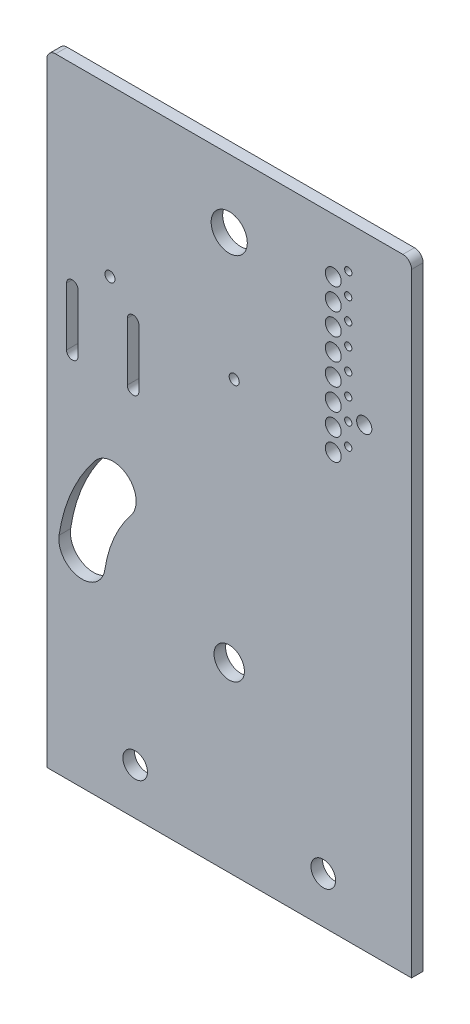
SolidWorks part; units mm, degrees
ref_plane "Ön Düzlem" through (0, 0, 0) normal (0, 0, 1) x (1, 0, 0)
ref_plane "Üst Düzlem" through (0, 0, 0) normal (0, 1, 0) x (1, 0, 0)
ref_plane "Sağ Düzlem" through (0, 0, 0) normal (1, 0, 0) x (0, 0, -1)
sketch "Model" plane through (0, 0, 0) normal (0, 0, 1) x (1, 0, 0)
  line L0 (2205.6968, 1653.3829) -> (2213.2595, 1658.0286) construction
  line L1 (2211.0042, 1661.2461) -> (2203.4116, 1656.7808) construction
  line L4 (2215.7762, 1634.375) -> (2223.3388, 1639.0206) construction
  line L5 (2221.0836, 1642.2381) -> (2213.4909, 1637.7728) construction
  line L8 (2098.8929, 1585.6212) -> (2224.8929, 1585.6212)
  line L9 (2224.8929, 1585.6212) -> (2224.8929, 1800.6212)
  line L10 (2224.8929, 1800.6212) -> (2098.8929, 1800.6212)
  line L11 (2098.8929, 1800.6212) -> (2098.8929, 1585.6212)
  circle A0 centre (2129.4379, 1602.5117) radius 4.5
  circle A1 centre (2194.4379, 1602.5117) radius 4.5
  circle A2 centre (2161.8929, 1777.1976) radius 6.25
  circle A3 centre (2161.8929, 1648.5151) radius 5.25
  circle A4 centre (2197.8384, 1781.8976) radius 2.75
  circle A5 centre (2203.0172, 1786.1566) radius 1.25
  circle A6 centre (2197.8336, 1774.3976) radius 2.75
  circle A7 centre (2203.0124, 1778.6566) radius 1.25
  circle A8 centre (2197.8347, 1766.8976) radius 2.75
  circle A9 centre (2203.0135, 1771.1566) radius 1.25
  circle A10 centre (2197.8341, 1759.3976) radius 2.75
  circle A11 centre (2203.0129, 1763.6566) radius 1.25
  circle A12 centre (2197.8353, 1751.8976) radius 2.75
  circle A13 centre (2203.0141, 1756.1566) radius 1.25
  circle A14 centre (2197.836, 1744.3976) radius 2.75
  circle A15 centre (2203.0148, 1748.6566) radius 1.25
  circle A16 centre (2197.8336, 1736.8976) radius 2.75
  circle A17 centre (2203.0124, 1741.1566) radius 1.25
  circle A18 centre (2197.8336, 1729.3976) radius 2.75
  circle A19 centre (2203.0124, 1733.6566) radius 1.25
  circle A20 centre (2208.5322, 1742.9332) radius 2.625
  circle A21 centre (2163.6193, 1734.1117) radius 1.75
  circle A22 centre (2120.6953, 1743.3824) radius 1.75
  spline S1 degree 3 poles (2213.2595, 1658.0286) (2213.935, 1660.1178) (2213.1833, 1661.1903) (2211.0042, 1661.2461) knots 0.25 0.25 0.25 0.25 0.375 0.375 0.375 0.375 construction
  spline S2 degree 2 poles (2203.4116, 1656.7808) (2202.3354, 1653.552) (2205.6968, 1653.3829) knots 0.75 0.75 0.75 1 1 1 construction
  spline S3 degree 3 poles (2223.3388, 1639.0206) (2224.0144, 1641.1098) (2223.2626, 1642.1823) (2221.0836, 1642.2381) knots 0.25 0.25 0.25 0.25 0.375 0.375 0.375 0.375 construction
  spline S4 degree 2 poles (2213.4909, 1637.7728) (2212.4148, 1634.544) (2215.7762, 1634.375) knots 0.75 0.75 0.75 1 1 1 construction
base flange "Taban-Flanş1" sketch "Model" thickness 4 reverse thickness direction no parameters "D1"=1.5
sketch "Çizim1" plane through (0, 0, 0) normal (0, 0, 1) x (1, 0, 0)
  line L1 (2104.3746, 1614.7539) -> (2206.551, 1614.7539)
  line L2 (2104.3746, 1614.7539) -> (2104.3746, 1592.6455)
  line L3 (2104.3746, 1592.6455) -> (2206.551, 1592.6455)
  line L4 (2206.551, 1614.7539) -> (2206.551, 1592.6455)
  line L5 (2104.3746, 1614.7539) -> (2206.551, 1592.6455) construction
  line L6 (2104.3746, 1592.6455) -> (2206.551, 1614.7539) construction
  point P0 (2155.4628, 1603.6997)
base flange "Sekme1" sketch "Çizim1" thickness 4 reverse thickness direction no parameters "D1"=1.5
sketch "Çizim4" plane through (0, 0, 0) normal (0, 0, 1) x (1, 0, 0)
  line L0 (2129.3929, 1601.6212) -> (2194.3929, 1601.6212) construction
  line L1 (2161.8929, 1800.6212) -> (2161.8929, 1601.6212) construction
  line L2 (2224.8929, 1800.6212) -> (2098.8929, 1800.6212) construction
  line L3 (2098.8929, 1585.6212) -> (2224.8929, 1585.6212) construction
  circle A0 centre (2129.3929, 1601.6212) radius 4.25
  circle A1 centre (2194.3929, 1601.6212) radius 4.25
  dimension "D3" = 8.5
  dimension "D1" = 65
  dimension "D2" = 16
extrude "Kes-Ekstrüzyon1" cut sketch "Çizim4" against normal blind 10 normal cut yes
sketch "Çizim7" plane through (0, 0, 0) normal (0, 0, 1) x (1, 0, 0)
  circle A0 centre (2161.8929, 1648.5151) radius 51.4198 construction
  arc A1 (2121.7368, 1680.6319) -> (2111.0254, 1656.0315) centre (2161.8929, 1648.5151) ccw construction
  arc A2 (2115.4893, 1685.6287) -> (2103.1113, 1657.2009) centre (2161.8929, 1648.5151) ccw
  arc A3 (2127.9844, 1675.6351) -> (2118.9395, 1654.8621) centre (2161.8929, 1648.5151) ccw
  arc A4 (2127.9844, 1675.6351) -> (2115.4893, 1685.6287) centre (2121.7368, 1680.6319) ccw
  arc A5 (2103.1113, 1657.2009) -> (2118.9395, 1654.8621) centre (2111.0254, 1656.0315) ccw
  point P5 (2114.7483, 1669.0427)
  dimension "D1" = 102.8397
  dimension "D2" = 16
extrude "Kes-Ekstrüzyon2" cut sketch "Çizim7" against normal blind 10 normal cut yes
sketch "Çizim9" plane through (0, 0, 0) normal (0, 0, 1) x (1, 0, 0)
  line L0 (2107.6845, 1733.9191) -> (2107.6845, 1713.9191) construction
  line L1 (2109.6845, 1733.9191) -> (2109.6845, 1713.9191)
  line L2 (2105.6845, 1733.9191) -> (2105.6845, 1713.9191)
  line L3 (2128.6845, 1733.9191) -> (2128.6845, 1713.9191) construction
  line L4 (2130.6845, 1733.9191) -> (2130.6845, 1713.9191)
  line L5 (2126.6845, 1733.9191) -> (2126.6845, 1713.9191)
  line L6 (2107.6845, 1723.9191) -> (2128.6845, 1723.9191) construction
  arc A0 (2109.6845, 1733.9191) -> (2105.6845, 1733.9191) centre (2107.6845, 1733.9191) ccw
  arc A1 (2105.6845, 1713.9191) -> (2109.6845, 1713.9191) centre (2107.6845, 1713.9191) ccw
  arc A2 (2130.6845, 1733.9191) -> (2126.6845, 1733.9191) centre (2128.6845, 1733.9191) ccw
  arc A3 (2126.6845, 1713.9191) -> (2130.6845, 1713.9191) centre (2128.6845, 1713.9191) ccw
  point P2 (2107.6845, 1723.9191)
  point P7 (2128.6845, 1723.9191)
  dimension "D1" = 2
  dimension "D2" = 21
  dimension "D3" = 20
extrude "Kes-Ekstrüzyon4" cut sketch "Çizim9" against normal blind 10 normal cut yes
fillet "Radyus1" radius 3 2 edges at (2098.8929, 1800.6212, -2) (2224.8929, 1800.6212, -2)
sketch "Büküm-Çizgileri1" [suppressed] plane through (0, 0, 0) normal (0, 1, 0) x (1, 0, 0)
sketch "Sınırlandırma-Kutusu1" [suppressed] plane through (0, 0, 0) normal (0, 1, 0) x (1, 0, 0)
sheet metal parameters "Sac-Levha1" thickness 4 parameters "D1"=1.5
flat pattern "Düz-Çoğaltma1" [suppressed]
sketch "Büküm-Çizgileri2" plane through (0, 0, 0) normal (0, 1, 0) x (1, 0, 0)
sketch3d "Sınırlandırma-Kutusu2" [suppressed]
  line L0 (-2224.8929, 1800.6212, 0) -> (-2224.8929, 1585.6212, 0) construction
  line L1 (-2098.8929, 1800.6212, 0) -> (-2098.8929, 1585.6212, 0) construction
  line L2 (-2224.8929, 1800.6212, 0) -> (-2098.8929, 1800.6212, 0) construction
  line L3 (-2224.8929, 1585.6212, 0) -> (-2098.8929, 1585.6212, 0) construction
sheet metal parameters "Sac-Levha2" thickness 4 parameters "D1"=1.5
flat pattern "Düz-Çoğaltma2"
sketch "Büküm-Çizgileri3" plane through (0, 0, 0) normal (0, 1, 0) x (1, 0, 0)
sketch3d "Sınırlandırma-Kutusu3" [suppressed]
  line L0 (2224.8929, 1800.6212, 0) -> (2224.8929, 1585.6212, 0) construction
  line L1 (2098.8929, 1800.6212, 0) -> (2098.8929, 1585.6212, 0) construction
  line L2 (2224.8929, 1800.6212, 0) -> (2098.8929, 1800.6212, 0) construction
  line L3 (2224.8929, 1585.6212, 0) -> (2098.8929, 1585.6212, 0) construction
sheet metal parameters "Sac-Levha3" thickness 4 parameters "D1"=1.5
flat pattern "Düz-Çoğaltma2"
sketch "Büküm-Çizgileri3" plane through (0, 0, 0) normal (0, 1, 0) x (1, 0, 0)
sketch3d "Sınırlandırma-Kutusu3" [suppressed]
  line L0 (2224.8929, 1800.6212, 0) -> (2224.8929, 1585.6212, 0) construction
  line L1 (2098.8929, 1800.6212, 0) -> (2098.8929, 1585.6212, 0) construction
  line L2 (2224.8929, 1800.6212, 0) -> (2098.8929, 1800.6212, 0) construction
  line L3 (2224.8929, 1585.6212, 0) -> (2098.8929, 1585.6212, 0) construction
sheet metal parameters "Sac-Levha4" thickness 4 parameters "D1"=1.5
flat pattern "Düz-Çoğaltma2"
sketch "Büküm-Çizgileri3" plane through (0, 0, 0) normal (0, 1, 0) x (1, 0, 0)
sketch3d "Sınırlandırma-Kutusu3" [suppressed]
  line L0 (2224.8929, 1800.6212, 0) -> (2224.8929, 1585.6212, 0) construction
  line L1 (2098.8929, 1800.6212, 0) -> (2098.8929, 1585.6212, 0) construction
  line L2 (2224.8929, 1800.6212, 0) -> (2098.8929, 1800.6212, 0) construction
  line L3 (2224.8929, 1585.6212, 0) -> (2098.8929, 1585.6212, 0) construction
sheet metal parameters "Sac-Levha6" thickness 4 parameters "D1"=1.5
flat pattern "Düz-Çoğaltma2"
sketch "Büküm-Çizgileri3" plane through (0, 0, 0) normal (0, 1, 0) x (1, 0, 0)
sketch3d "Sınırlandırma-Kutusu3" [suppressed]
  line L0 (2224.8929, 1585.6212, 0) -> (2224.8929, 1800.6212, 0) construction
  line L1 (2098.8929, 1585.6212, 0) -> (2098.8929, 1800.6212, 0) construction
  line L2 (2224.8929, 1585.6212, 0) -> (2098.8929, 1585.6212, 0) construction
  line L3 (2224.8929, 1800.6212, 0) -> (2098.8929, 1800.6212, 0) construction
